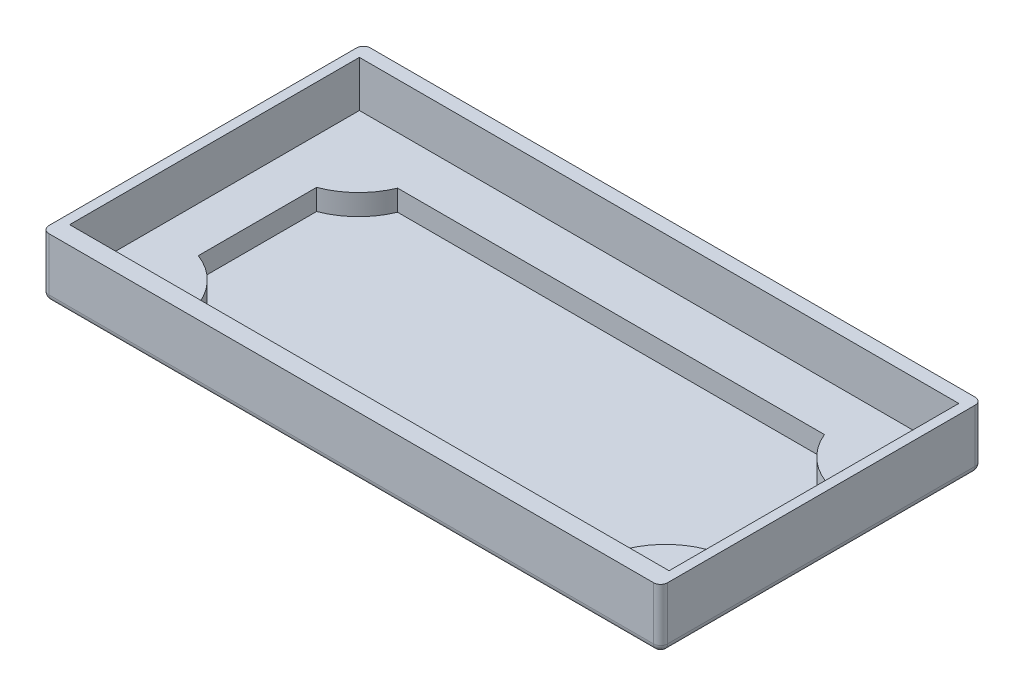
SolidWorks part; units mm, degrees
ref_plane "Alzado" through (0, 0, 0) normal (0, 0, 1) x (1, 0, 0)
ref_plane "Planta" through (0, 0, 0) normal (0, 1, 0) x (1, 0, 0)
ref_plane "Vista lateral" through (0, 0, 0) normal (1, 0, 0) x (0, 0, -1)
sketch "Top-cover-sketch-01" plane through (0, 0, 0) normal (0, 1, 0) x (1, 0, 0)
  line L1 (-22.185, 11.53) -> (22.185, 11.53)
  line L2 (-22.185, 11.53) -> (-22.185, -11.53)
  line L3 (-22.185, -11.53) -> (22.185, -11.53)
  line L4 (22.185, 11.53) -> (22.185, -11.53)
  line L5 (-22.185, 11.53) -> (22.185, -11.53) construction
  line L6 (-22.185, -11.53) -> (22.185, 11.53) construction
  line L7 (-20.105, -9.1) -> (20.105, -9.1) construction
  line L8 (-20.105, -9.1) -> (-20.105, 9.1) construction
  line L9 (-20.105, 9.1) -> (20.105, 9.1) construction
  line L10 (20.105, -9.1) -> (20.105, 9.1) construction
  line L11 (-20.105, -9.1) -> (20.105, 9.1) construction
  line L12 (-20.105, 9.1) -> (20.105, -9.1) construction
  line L13 (-16.0258, 8.1) -> (16.0258, 8.1)
  line L15 (-16.0258, -8.1) -> (16.0258, -8.1)
  line L16 (19.255, 4.9869) -> (19.255, -4.9869)
  line L24 (-19.255, -4.9869) -> (-19.255, 4.9869)
  circle A0 centre (-20.105, 9.1) radius 0.85
  circle A1 centre (20.105, 9.1) radius 0.85
  circle A2 centre (20.105, -9.1) radius 0.85
  circle A3 centre (-20.105, -9.1) radius 0.85
  arc A4 (19.255, -4.9869) -> (16.0258, -8.1) centre (20.105, -9.1) ccw
  arc A5 (16.0258, 8.1) -> (19.255, 4.9869) centre (20.105, 9.1) ccw
  arc A6 (-19.255, 4.9869) -> (-16.0258, 8.1) centre (-20.105, 9.1) ccw
  arc A7 (-19.255, -4.9869) -> (-16.0258, -8.1) centre (-20.105, -9.1) cw
  point P0 (0, 0)
  point P6 (0, 0)
  dimension "D5" = 1.7
  dimension "D1" = 23.06
  dimension "D2" = 44.37
  dimension "D3" = 18.2
  dimension "D4" = 40.21
  dimension "D6" = 2.93
  dimension "D9" = 3.43
  dimension "D15" = 2.93
extrude "Top-cover-ext-shape" add sketch "Top-cover-sketch-01" along normal blind 4.3 contours L3 L4 L1 L2
extrude "Saliente-Extruir1" add sketch "Top-cover-sketch-01<18>" against normal blind 1.5 contours L24 A7 L15 A4 L16 A5 L13 A6 region at (0, 0, 0)
sketch "Top-cover-sketch-01<18>" plane through (0, 0, 0) normal (0, 1, 0) x (1, 0, 0) same geometry as "Top-cover-sketch-01"
shell "Vaciado1" thickness 1 removed face at (0, 4.3, 0)
sketch "Croquis1" plane through (0, -1.5, 0) normal (0, -1, 0) x (1, 0, 0)
  circle A0 centre (-11.8789, 0) radius 3.25
  circle A1 centre (-11.8789, 0) radius 5
extrude "Cortar-Extruir1" cut sketch "Croquis1" against normal blind 0.7 contours A0 region at (-11.8789, -1.5, 0)
extrude "Cortar-Extruir2" cut sketch "Croquis1<5>" against normal blind 0.5 contours A1 A0 region at (-16.7375, -1.5, 0)
sketch "Croquis1<5>" plane through (0, -1.5, 0) normal (0, -1, 0) x (1, 0, 0) same geometry as "Croquis1"
sketch "Croquis2" plane through (0, -0.8, 0) normal (0, -1, 0) x (1, 0, 0)
  line L0 (-22.185, -11.53) -> (-22.185, 11.53) construction
  circle A0 centre (-11.8789, 0) radius 3
extrude "Saliente-Extruir2" add sketch "Croquis2" along normal blind 4.7
fillet "Redondeo1" radius 0.5 8 edges at (22.185, 2.15, 11.53) (22.185, 2.15, -11.53) (-22.185, 0, 0) (22.185, 0, 0) (0, 0, 11.53) (-22.185, 2.15, 11.53) (-22.185, 2.15, -11.53) (0, 0, -11.53)
